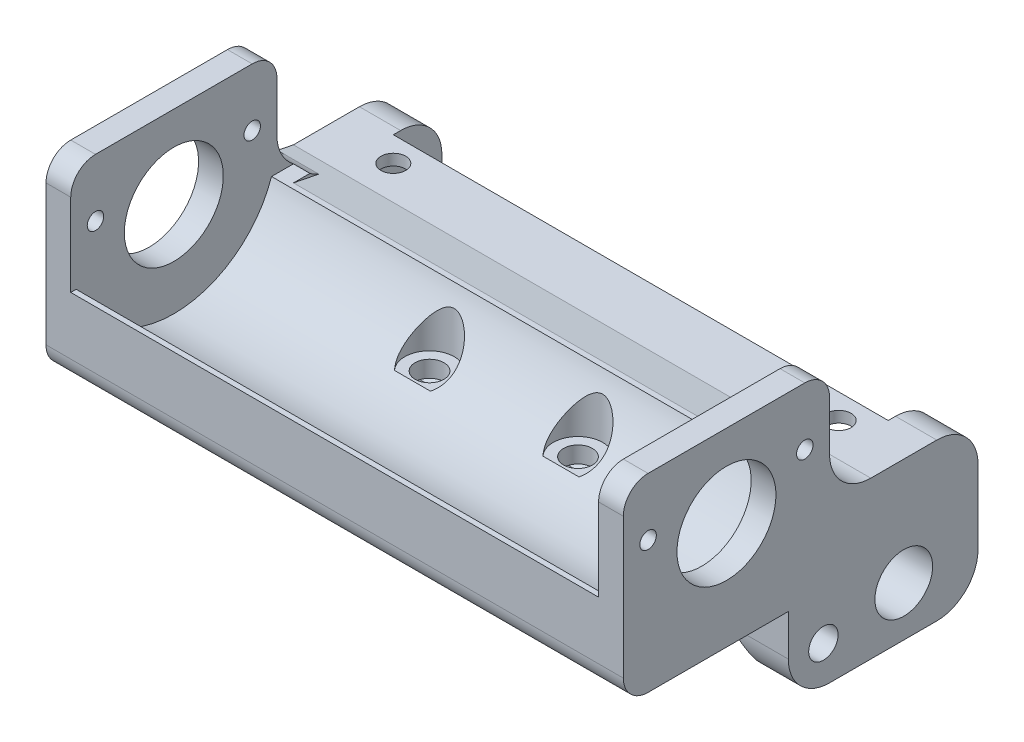
SolidWorks part; units mm, degrees
ref_plane "Front Plane" through (0, 0, 0) normal (0, 0, 1) x (1, 0, 0)
ref_plane "Top Plane" through (0, 0, 0) normal (0, 1, 0) x (1, 0, 0)
ref_plane "Right Plane" through (0, 0, 0) normal (1, 0, 0) x (0, 0, -1)
sketch "Sketch1" plane through (0, 0, 0) normal (0, 1, 0) x (1, 0, 0)
  line L1 (-35, 12.5) -> (35, 12.5)
  line L2 (-35, 12.5) -> (-35, -12.5)
  line L3 (-35, -12.5) -> (35, -12.5)
  line L4 (35, 12.5) -> (35, -12.5)
  line L5 (-35, 12.5) -> (35, -12.5) construction
  line L6 (-35, -12.5) -> (35, 12.5) construction
  point P0 (0, 0)
  dimension "D1" = 70
  dimension "D2" = 25
extrude "Boss-Extrude1" add sketch "Sketch1" along normal blind 10
sketch "Sketch2" plane through (0, 10, 0) normal (0, 1, 0) x (1, 0, 0)
  line L0 (-35, -12.5) -> (35, -12.5) construction
  line L1 (-35, 12.5) -> (-32, 12.5)
  line L2 (-35, 12.5) -> (-35, -12.5)
  line L3 (-35, -12.5) -> (-32, -12.5)
  line L4 (-32, 12.5) -> (-32, -12.5)
  dimension "D1" = 3
extrude "Boss-Extrude2" add sketch "Sketch2" along normal blind 13
sketch "Sketch3" plane through (35, 0, 0) normal (1, 0, 0) x (0, 0, -1)
  line L0 (-12.5, 0) -> (12.5, 0) construction
  circle A0 centre (0, 14) radius 12.5
  dimension "D1" = 25
  dimension "D2" = 14
extrude "Cut-Extrude1" cut sketch "Sketch3" against normal blind 67
ref_plane "Plane1" through (0, 3, 0) normal (0, 1, 0) x (1, 0, 0)
sketch "Sketch4" plane through (0, 3, 0) normal (0, 1, 0) x (1, 0, 0)
  line L0 (-9, 8) -> (9, 8) construction
  circle A0 centre (-9, 8) radius 3
  circle A1 centre (9, 8) radius 3
  dimension "D4" = 6
  dimension "D5" = 6
  dimension "D1" = 9
  dimension "D2" = 9
  dimension "D3" = 8
extrude "Cut-Extrude2" cut sketch "Sketch4" along normal through all
sketch "Sketch5" plane through (0, 3, 0) normal (0, 1, 0) x (1, 0, 0)
  circle A0 centre (-9, 8) radius 1.75
  circle A1 centre (9, 8) radius 1.75
  dimension "D1" = 3.5
  dimension "D2" = 3.5
extrude "Cut-Extrude3" cut sketch "Sketch5" against normal through all
sketch "Sketch6" plane through (0, 0, 0) normal (0, -1, 0) x (1, 0, 0)
  line L0 (35, -12.5) -> (-35, -12.5) construction
  line L1 (-14.5, -12.5) -> (14.5, -12.5)
  line L2 (-14.5, -12.5) -> (-14.5, 0.5)
  line L3 (-14.5, 0.5) -> (14.5, 0.5)
  line L4 (14.5, -12.5) -> (14.5, 0.5)
  line L5 (0, 0) -> (0, 0.5) construction
  dimension "D1" = 29
  dimension "D2" = 13
extrude "Cut-Extrude4" cut sketch "Sketch6" against normal blind 1
mirror "Mirror1" about plane through (0, 0, 0) normal (0, 0, 1) of "Cut-Extrude4", "Cut-Extrude3", "Cut-Extrude2"
sketch "Sketch9" plane through (35, 0, 0) normal (1, 0, 0) x (0, 0, -1)
  line L1 (-12.5, 0) -> (12.5, 0)
  line L2 (-12.5, 0) -> (-12.5, 23)
  line L3 (-12.5, 23) -> (12.5, 23)
  line L4 (12.5, 0) -> (12.5, 23)
extrude "Boss-Extrude3" add sketch "Sketch9" against normal blind 3
sketch "Sketch8" plane through (-35, 0, 0) normal (-1, 0, 0) x (0, 0, 1)
  line L0 (0, 13) -> (0, 0) construction
  line L1 (9.5, 16) -> (-9.5, 16) construction
  circle A0 centre (0, 13) radius 6
  circle A1 centre (-9.5, 16) radius 1
  circle A2 centre (9.5, 16) radius 1
  dimension "D2" = 12
  dimension "D6" = 2
  dimension "D7" = 2
  dimension "D1" = 13
  dimension "D3" = 3
  dimension "D4" = 9.5
  dimension "D5" = 9.5
extrude "Cut-Extrude6" cut sketch "Sketch8" against normal through all
fillet "Fillet1" radius 3 4 edges at (33.5, 23, -12.5) (33.5, 23, 12.5) (-33.5, 23, -12.5) (-33.5, 23, 12.5)
sketch "Sketch10" plane through (35, 0, 0) normal (1, 0, 0) x (0, 0, -1)
  line L0 (12.5, 20) -> (12.5, 0) construction
  line L1 (12.3195, 9) -> (30.5, 9)
  line L2 (7.5, 0.4196) -> (7.5, -10)
  line L3 (7.5, -10) -> (30.5, -10)
  line L4 (30.5, 9) -> (30.5, -10)
  line L5 (-12.5, 0) -> (12.5, 0) construction
  line L6 (12.3195, 9) -> (7.5, 0.4196)
  dimension "D1" = 5
  dimension "D2" = 9
  dimension "D3" = 19
extrude "Boss-Extrude4" add sketch "Sketch10" against normal blind 5
fillet "Fillet2" radius 5 3 edges at (32.5, -10, -30.5) (32.5, 9, -30.5) (32.5, -10, -7.5)
sketch "Sketch11" plane through (35, 0, 0) normal (1, 0, 0) x (0, 0, -1)
  line L0 (30.5, -5) -> (30.5, 4) construction
  line L1 (25.5, 9) -> (12.5, 9) construction
  circle A0 centre (21.5, -4) radius 3.5
  dimension "D3" = 7
  dimension "D1" = 9
  dimension "D2" = 13
extrude "Cut-Extrude7" cut sketch "Sketch11" against normal through all
mirror "Mirror2" about plane through (0, 0, 0) normal (1, 0, 0) of "Cut-Extrude7", "Fillet2", "Boss-Extrude4"
fillet "Fillet3" radius 5 2 edges at (-32.5, 9, -12.5) (32.5, 9, -12.5)
fillet "Fillet4" radius 3 2 edges at (24.75, 0, 12.5) (-22.25, 0, -12.5)
sketch "Sketch12" plane through (-35, 0, 0) normal (-1, 0, 0) x (0, 0, 1)
  circle A0 centre (-11.7553, -5.4608) radius 1.7844
extrude "Cut-Extrude8" cut sketch "Sketch12" against normal through all
sketch "Sketch13" plane through (30, 0, 0) normal (-1, 0, 0) x (0, 0, 1)
  line L9 (-12.5, 10) -> (-12.5, 3)
  line L10 (-12.5, 3) -> (-9.5, 0)
  line L11 (-7.5, 0) -> (-9.5, 0) construction
  line L12 (-9.5, 0) -> (-7.5, 0)
  line L13 (-7.5, 0) -> (-7.5, -5)
  line L14 (-7.5, -5) -> (-16.5394, 7.6551)
  line L15 (-17.5, 9) -> (-12.5, 10)
  line L16 (-17.5, 9) -> (-24.6125, 9)
  line L17 (-25.5, 9) -> (-17.5, 9) construction
  line L18 (-24.6125, 9) -> (-24.6125, 7.6551)
  line L19 (-24.6125, 7.6551) -> (-16.5394, 7.6551)
  arc A2 (-12.5, 3) -> (-9.5, 0) centre (-9.5, 3) ccw construction
extrude "Boss-Extrude5" add sketch "Sketch13" along normal blind 65
fillet "Fillet5" radius 3 2 edges at (-30, 1.3276, -12.0197) (30, 1.3276, -12.0197)
sketch "Sketch14" plane through (0, 9, 0) normal (0, 1, 0) x (1, 0, 0)
  line L0 (-35, 25.5) -> (-35, 17.5) construction
  line L1 (-30, 24.6125) -> (30, 24.6125) construction
  line L2 (35, 25.5) -> (35, 17.5) construction
  circle A0 centre (-27, 21.6125) radius 1.5
  circle A1 centre (27, 21.6125) radius 1.5
  point P8 (-27.404, 23.071)
  dimension "D1" = 3
  dimension "D3" = 3
  dimension "D4" = 3
  dimension "D5" = 3
  dimension "D6" = 8
  dimension "D2" = 8
extrude "Cut-Extrude9" cut sketch "Sketch14" against normal blind 10
